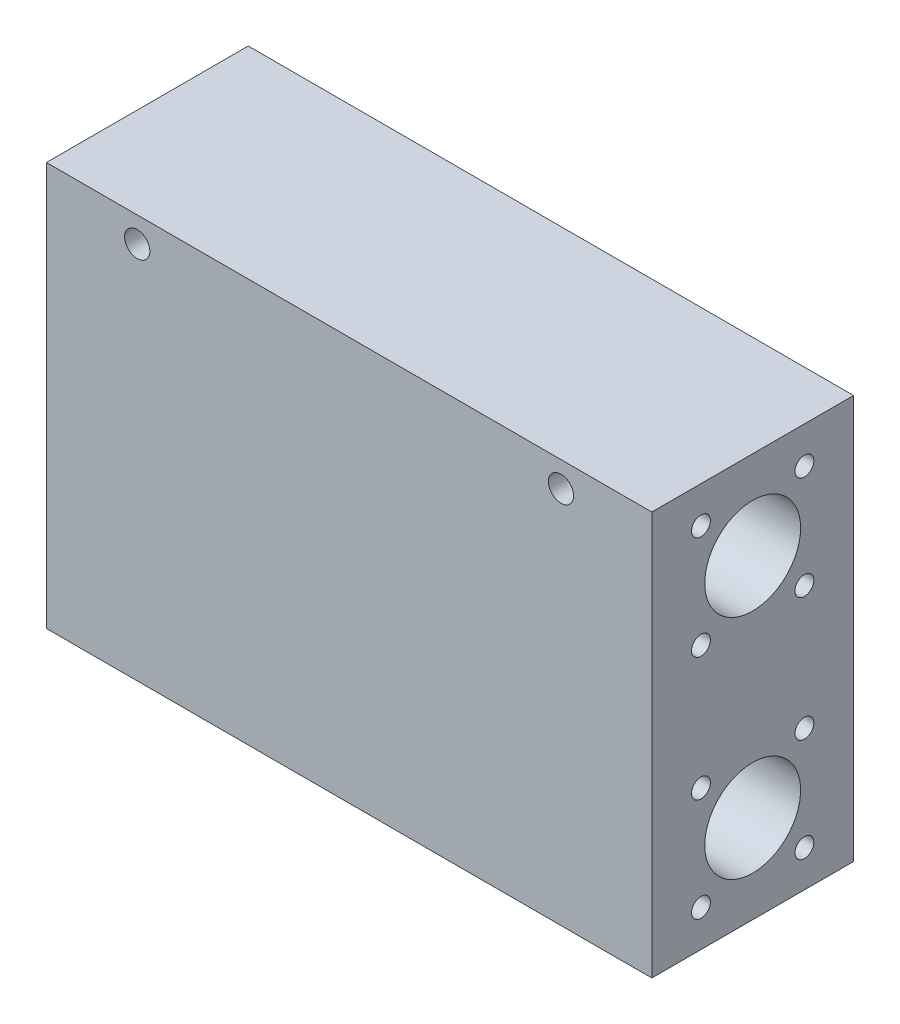
SolidWorks part; units mm, degrees
material "1060 Alloy"
ref_plane "Front Plane" through (0, 0, 0) normal (0, 0, 1) x (1, 0, 0)
ref_plane "Top Plane" through (0, 0, 0) normal (0, 1, 0) x (1, 0, 0)
ref_plane "Right Plane" through (0, 0, 0) normal (1, 0, 0) x (0, 0, -1)
sketch "Sketch1" plane through (0, 0, 0) normal (0, 0, 1) x (1, 0, 0)
  line L1 (0, 0) -> (120, 0)
  line L2 (0, 0) -> (0, 80)
  line L3 (0, 80) -> (120, 80)
  line L4 (120, 0) -> (120, 80)
  dimension "D1" = 80
  dimension "D2" = 120
extrude "Boss-Extrude1" add sketch "Sketch1" along normal blind 40 contours L3 L4 L1 L2
sketch "Sketch2" plane through (0, 0, 0) normal (-1, 0, 0) x (0, 0, 1)
  line L0 (20, 80) -> (20, 0) construction
  line L1 (40, 80) -> (0, 80) construction
  line L2 (40, 0) -> (0, 0) construction
  line L3 (40, 40) -> (0, 40) construction
  line L4 (40, 0) -> (40, 80) construction
  line L5 (0, 0) -> (0, 80) construction
  line L6 (0, 62.5) -> (40, 62.5) construction
  line L7 (0, 17.5) -> (40, 17.5) construction
  circle A1 centre (30.25, 72.75) radius 1.85
  circle A2 centre (9.75, 72.75) radius 1.85
  circle A3 centre (30.25, 52.25) radius 1.85
  circle A4 centre (9.75, 52.25) radius 1.85
  circle A5 centre (9.75, 27.75) radius 1.85
  circle A6 centre (30.25, 27.75) radius 1.85
  circle A7 centre (30.25, 7.25) radius 1.85
  circle A9 centre (9.75, 7.25) radius 1.85
  dimension "D4" = 3.7
  dimension "D1" = 22.5
  dimension "D2" = 9.75
  dimension "D3" = 7.25
extrude "linear-bearing-screw-cuts" cut sketch "Sketch2" against normal blind 14
sketch "Sketch3" plane through (0, 0, 0) normal (-1, 0, 0) x (0, 0, 1)
  line L0 (20, 80) -> (20, 0) construction
  line L1 (40, 80) -> (0, 80) construction
  line L2 (40, 0) -> (0, 0) construction
  line L3 (0, 40) -> (40, 40) construction
  line L4 (0, 0) -> (0, 80) construction
  line L5 (40, 0) -> (40, 80) construction
  line L6 (0, 62.5) -> (40, 62.5) construction
  line L7 (0, 17.5) -> (40, 17.5) construction
  circle A0 centre (20, 62.5) radius 9.5
  circle A2 centre (20, 17.5) radius 9.5
  dimension "D2" = 19
  dimension "D1" = 45
extrude "linear-bearings-hole" cut sketch "Sketch3" against normal blind 55
sketch "Sketch4" plane through (120, 0, 0) normal (1, 0, 0) x (0, 0, -1)
  line L0 (-20, 80) -> (-20, 0) construction
  line L1 (-40, 80) -> (0, 80) construction
  line L2 (-40, 0) -> (0, 0) construction
  line L3 (-40, 40) -> (0, 40) construction
  line L4 (-40, 0) -> (-40, 80) construction
  line L5 (0, 0) -> (0, 80) construction
  line L6 (-40, 62.5) -> (0, 62.5) construction
  line L7 (-40, 17.5) -> (0, 17.5) construction
  circle A0 centre (-9.75, 72.75) radius 1.875
  circle A1 centre (-30.25, 72.75) radius 1.875
  circle A2 centre (-9.75, 52.25) radius 1.875
  circle A3 centre (-30.25, 52.25) radius 1.875
  circle A4 centre (-30.25, 27.75) radius 1.875
  circle A5 centre (-9.75, 27.75) radius 1.875
  circle A6 centre (-9.75, 7.25) radius 1.875
  circle A7 centre (-30.25, 7.25) radius 1.875
  dimension "D2" = 3.75
  dimension "D1" = 45
  dimension "D3" = 7.25
  dimension "D4" = 9.75
extrude "linear-bearing-screw-cuts2" cut sketch "Sketch4" against normal blind 14
sketch "Sketch5" plane through (120, 0, 0) normal (1, 0, 0) x (0, 0, -1)
  line L0 (-20, 80) -> (-20, 0) construction
  line L1 (-40, 80) -> (0, 80) construction
  line L2 (-40, 0) -> (0, 0) construction
  line L3 (0, 40) -> (-40, 40) construction
  line L4 (0, 0) -> (0, 80) construction
  line L5 (-40, 0) -> (-40, 80) construction
  line L6 (-40, 62.5) -> (0, 62.5) construction
  line L7 (-40, 17.5) -> (0, 17.5) construction
  circle A0 centre (-20, 62.5) radius 9.5
  circle A1 centre (-20, 17.5) radius 9.5
  dimension "D2" = 19
  dimension "D1" = 45
extrude "linear-bearings-hole2" cut sketch "Sketch5" against normal blind 55
sketch "Sketch11" plane through (0, 0, 40) normal (0, 0, 1) x (1, 0, 0)
  line L0 (0, 0) -> (120, 0) construction
  line L1 (0, 0) -> (0, 80) construction
  line L2 (120, 0) -> (120, 80) construction
  circle A0 centre (5.5, 35) radius 1.25
  circle A1 centre (36.5, 35) radius 1.25
  circle A2 centre (83.5, 35) radius 1.25
  circle A3 centre (114.5, 35) radius 1.25
  circle A4 centre (5.5, 4) radius 1.25
  circle A5 centre (36.5, 4) radius 1.25
  circle A6 centre (83.5, 4) radius 1.25
  circle A7 centre (114.5, 4) radius 1.25
  dimension "D7" = 2.5
  dimension "D1" = 4
  dimension "D2" = 31
  dimension "D3" = 31
  dimension "D4" = 5.5
  dimension "D5" = 31
  dimension "D6" = 5.5
extrude "Cut-Extrude8" [suppressed] cut sketch "Sketch11" against normal through all
sketch "Sketch12" plane through (65, 0, 0) normal (1, 0, 0) x (0, 0, -1)
  circle A0 centre (-20, 62.5) radius 6
  circle A1 centre (-20, 17.5) radius 6
  dimension "D1" = 12
extrude "Cut-Extrude9" cut sketch "Sketch12" against normal through all
sketch "Sketch13" plane through (0, 0, 0) normal (0, 0, -1) x (-1, 0, 0)
  line L0 (0, 80) -> (-120, 80) construction
  line L1 (-120, 0) -> (-120, 80) construction
  line L2 (0, 0) -> (0, 80) construction
  circle A0 centre (-102, 75) radius 2.5
  circle A1 centre (-18, 75) radius 2.5
  dimension "D4" = 5
  dimension "D1" = 5
  dimension "D2" = 18
  dimension "D3" = 18
extrude "Cut-Extrude10" cut sketch "Sketch13" against normal through all
